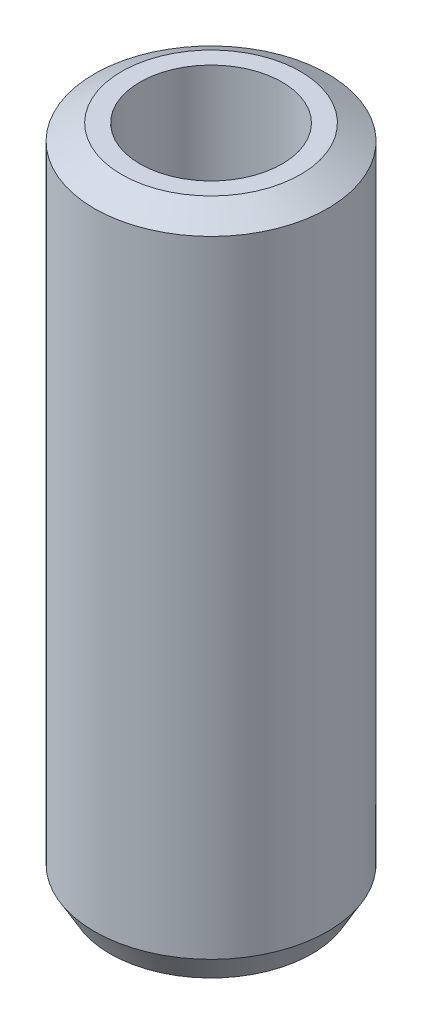
SolidWorks part; units mm, degrees
ref_plane "Front Plane" through (0, 0, 0) normal (0, 0, 1) x (1, 0, 0)
ref_plane "Top Plane" through (0, 0, 0) normal (0, 1, 0) x (1, 0, 0)
ref_plane "Right Plane" through (0, 0, 0) normal (1, 0, 0) x (0, 0, -1)
sketch "Sketch1" plane through (0, 0, 0) normal (0, 1, 0) x (1, 0, 0)
  circle A0 centre (0, 0) radius 17.5
  dimension "SHAFT_OD" = 35
extrude "Boss-Extrude1" add sketch "Sketch1" along normal blind 100.3605
sketch "Sketch2" plane through (0, 0, 0) normal (0, 1, 0) x (1, 0, 0)
  circle A0 centre (0, 0) radius 10.653
  dimension "BORE_D" = 21.306
extrude "Cut-Extrude1" cut sketch "Sketch2" along normal through all
chamfer "Chamfer1" distance 2.3625 angle 60 2 edges at (0, 100.3605, 17.5) (0, 0, 17.5) first distance on face at (0, 100.3605, 17.5) first distance on face at (0, 0, 10.653)
